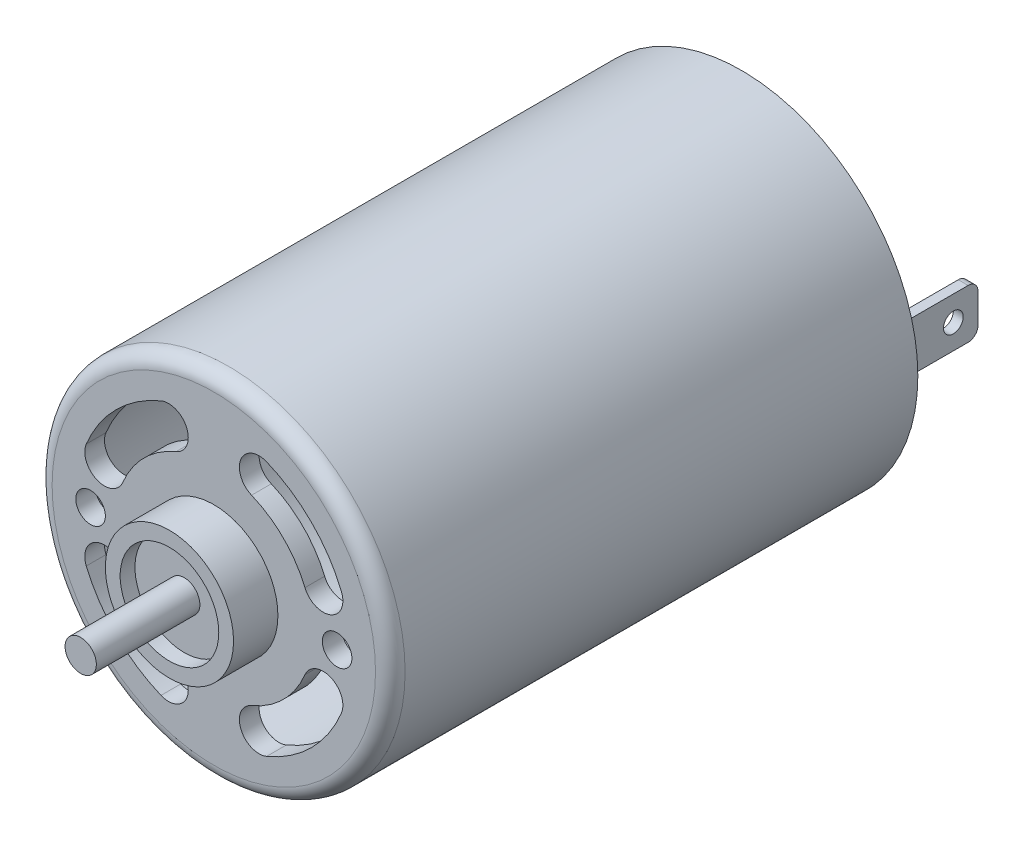
SolidWorks part; units mm, degrees
ref_plane "Спереди" through (0, 0, 0) normal (0, 0, 1) x (1, 0, 0)
ref_plane "Сверху" through (0, 0, 0) normal (0, 1, 0) x (1, 0, 0)
ref_plane "Справа" through (0, 0, 0) normal (1, 0, 0) x (0, 0, -1)
sketch "Эскиз1" plane through (0, 0, 0) normal (0, 0, 1) x (1, 0, 0)
  line L0 (28.5, 0) -> (-30.0333, 0) construction
  line L1 (-15, 2.5) -> (-14, 2.5)
  line L2 (14, 2.5) -> (15, 2.5)
  line L3 (14, 2.5) -> (14, -2.5)
  line L4 (14, -2.5) -> (15, -2.5)
  line L5 (15, 2.5) -> (15, -2.5)
  line L6 (-15, 2.5) -> (-15, -2.5)
  line L7 (-15, -2.5) -> (-14, -2.5)
  line L8 (-14, 2.5) -> (-14, -2.5)
  circle A0 centre (0, 0) radius 17.9
  circle A1 centre (0, 0) radius 17
  circle A2 centre (0, 0) radius 7.5
  circle A3 centre (0, 0) radius 1.585
  circle A4 centre (0, 0) radius 12
  dimension "D1" = 14
  dimension "D3" = 35.8
  dimension "D2" = 2
extrude "Бобышка-Вытянуть1" add sketch "Эскиз1" along normal blind 53.5 contours A0
sketch "Эскиз2" plane through (0, 0, 53.5) normal (0, 0, 1) x (1, 0, 0)
  circle A0 centre (0, 0) radius 6.5
  circle A1 centre (12.5, 0) radius 1.5
  circle A2 centre (-12.5, 0) radius 1.5
  arc A3 (-3.8268, 9.2388) -> (-9.2388, 3.8268) centre (0, 0) ccw
  arc A4 (-5.3576, 12.9343) -> (-12.9343, 5.3576) centre (0, 0) ccw
  arc A5 (12.9343, 5.3576) -> (5.3576, 12.9343) centre (0, 0) ccw
  arc A6 (-3.8268, 9.2388) -> (-5.3576, 12.9343) centre (-4.5922, 11.0866) ccw
  arc A7 (5.3576, 12.9343) -> (3.8268, 9.2388) centre (4.5922, 11.0866) ccw
  arc A8 (9.2388, 3.8268) -> (12.9343, 5.3576) centre (11.0866, 4.5922) ccw
  arc A9 (12.9343, -5.3576) -> (9.2388, -3.8268) centre (11.0866, -4.5922) ccw
  arc A10 (3.8268, -9.2388) -> (5.3576, -12.9343) centre (4.5922, -11.0866) ccw
  arc A11 (-5.3576, -12.9343) -> (-3.8268, -9.2388) centre (-4.5922, -11.0866) ccw
  arc A12 (-9.2388, -3.8268) -> (-12.9343, -5.3576) centre (-11.0866, -4.5922) ccw
  arc A13 (-12.9343, 5.3576) -> (-9.2388, 3.8268) centre (-11.0866, 4.5922) ccw
  arc A14 (9.2388, 3.8268) -> (3.8268, 9.2388) centre (0, 0) ccw
  arc A15 (3.8268, -9.2388) -> (9.2388, -3.8268) centre (0, 0) ccw
  arc A16 (5.3576, -12.9343) -> (12.9343, -5.3576) centre (0, 0) ccw
  arc A17 (-9.2388, -3.8268) -> (-3.8268, -9.2388) centre (0, 0) ccw
  arc A18 (-12.9343, -5.3576) -> (-5.3576, -12.9343) centre (0, 0) ccw
  point P42 (0, 0)
extrude "Бобышка-Вытянуть2" add sketch "Эскиз2" along normal blind 4.5 contours A0
extrude "Вырез-Вытянуть1" cut sketch "Эскиз2<3>" against normal blind 10 contours A2 | A1
sketch "Эскиз2<3>" plane through (0, 0, 53.5) normal (0, 0, 1) x (1, 0, 0) same geometry as "Эскиз2"
sketch "Эскиз5" plane through (0, 0, 58) normal (0, 0, 1) x (1, 0, 0)
  circle A0 centre (0, 0) radius 1.585
  circle A1 centre (0, 0) radius 5
  dimension "D1" = 3.17
extrude "Бобышка-Вытянуть3" add sketch "Эскиз5" along normal blind 9 contours A0
extrude "Вырез-Вытянуть2" cut sketch "Эскиз5<3>" against normal blind 1.5
sketch "Эскиз5<3>" plane through (0, 0, 58) normal (0, 0, 1) x (1, 0, 0) same geometry as "Эскиз5"
extrude "Вырез-Вытянуть3" cut sketch "Эскиз2<4>" against normal blind 5 contours A4 A13 A3 A6 | A5 A7 A14 A8 | A15 A9 A16 A10 | A17 A11 A18 A12
sketch "Эскиз2<4>" plane through (0, 0, 53.5) normal (0, 0, 1) x (1, 0, 0) same geometry as "Эскиз2"
ref_plane "Плоскость1" through (0, 0, 3) normal (0, 0, 1) x (1, 0, 0)
sketch "Эскиз8" plane through (0, 0, 3) normal (0, 0, 1) x (1, 0, 0)
  circle A0 centre (0, 0) radius 16
extrude "Вырез-Вытянуть4" cut sketch "Эскиз8" along normal blind 48.5
extrude "Бобышка-Вытянуть5" add sketch "Эскиз1<5>" against normal blind 4.5 contours A2
sketch "Эскиз1<5>" plane through (0, 0, 0) normal (0, 0, 1) x (1, 0, 0) same geometry as "Эскиз1"
extrude "Вырез-Вытянуть6" cut sketch "Эскиз1<7>" along normal blind 2 contours L0 A1 L6 A4 L3 L2 L5 | A1 L0 L5 L4 L3 A4 L6 region at (0, -16.6199, 0) region at (16, 0.3801, 0)
sketch "Эскиз1<7>" plane through (0, 0, 0) normal (0, 0, 1) x (1, 0, 0) same geometry as "Эскиз1"
extrude "Бобышка-Вытянуть6" add sketch "Эскиз1<8>" against normal blind 9 contours L0 L5 L2 L3 | L6 L7 L8 L1 | L5 L4 L3 L2 region at (14.5, 1.25, 0)
sketch "Эскиз1<8>" plane through (0, 0, 0) normal (0, 0, 1) x (1, 0, 0) same geometry as "Эскиз1"
fillet "Скругление5" radius 1 1 edges at (12, 0, 0)
fillet "Скругление9" radius 1 1 edges at (7.5, 0, -4.5)
sketch "Эскиз10" plane through (15, 0, 0) normal (1, 0, 0) x (0, 0, -1)
  line L0 (9, 2.5) -> (9, -2.5) construction
  circle A0 centre (6.5, 0) radius 1
  point P2 (9, 0)
  dimension "D1" = 2.5
fillet "Скругление10" radius 1.5 1 edges at (17.9, 0, 53.5)
extrude "Вырез-Вытянуть9" cut sketch "Эскиз10" against normal up to surface (1 mm away) up to face at (14, 0, -3.5)
sketch "Эскиз11" plane through (-15, 0, 0) normal (-1, 0, 0) x (0, 0, 1)
  line L0 (-9, 2.5) -> (-9, -2.5) construction
  circle A0 centre (-6.5, 0) radius 1
  point P2 (-9, 0)
  dimension "D1" = 2.5
extrude "Вырез-Вытянуть10" cut sketch "Эскиз11" against normal up to surface (1 mm away) up to face at (-14, 0, -3.5)
fillet "Скругление11" radius 1 4 edges at (-14.5, 2.5, -9) (-14.5, -2.5, -9) (14.5, -2.5, -9) (14.5, 2.5, -9)
sketch "Эскиз12" plane through (0, 0, -4.5) normal (0, 0, -1) x (-1, 0, 0)
  circle A0 centre (0, 0) radius 5.5
extrude "Вырез-Вытянуть11" cut sketch "Эскиз12" against normal blind 2
sketch "Эскиз13" plane through (0, 0, -2.5) normal (0, 0, -1) x (-1, 0, 0)
  circle A1 centre (0, 0) radius 1.585
  dimension "D1" = 3.17
extrude "Бобышка-Вытянуть7" add sketch "Эскиз13" along normal blind 8
fillet "Скругление20" radius 0.5 1 edges at (-1.585, 0, -10.5)
